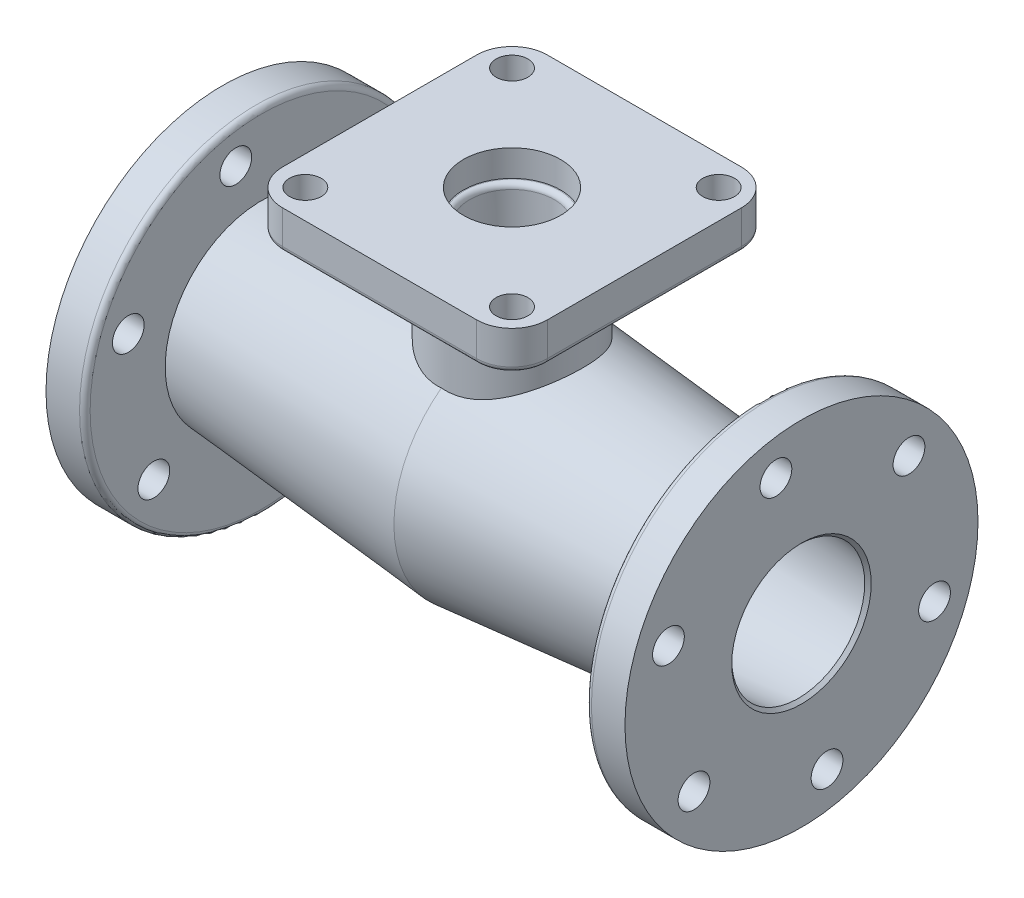
SolidWorks part; units mm, degrees
ref_plane "Front Plane" through (0, 0, 0) normal (0, 0, 1) x (1, 0, 0)
ref_plane "Top Plane" through (0, 0, 0) normal (0, 1, 0) x (1, 0, 0)
ref_plane "Right Plane" through (0, 0, 0) normal (1, 0, 0) x (0, 0, -1)
sketch "Sketch1" plane through (0, 0, 0) normal (0, 0, 1) x (1, 0, 0)
  line L0 (0, 0) -> (0, -50000) construction
  line L1 (0, 0) -> (-50000, 0) construction
  line L2 (0, -51.8481) -> (-164, -37.5)
  line L3 (-164, -37.5) -> (-164, -100)
  line L4 (-164, -100) -> (-142, -100)
  line L5 (-142, -100) -> (-142, -54.482)
  line L6 (-142, -54.482) -> (0, -66.9054)
  line L7 (142, -100) -> (142, -54.482)
  line L8 (164, -100) -> (142, -100)
  line L9 (164, -37.5) -> (164, -100)
  line L10 (0, -51.8481) -> (164, -37.5)
  line L11 (142, -54.482) -> (0, -66.9054)
  point P17 (-19.9552, -116.4925)
  point P18 (68.5947, -108.0282)
  dimension "D1" = 5
  dimension "D2" = 22
  dimension "D3" = 284
  dimension "D4" = 15
  dimension "D5" = 328
  dimension "D6" = 200
  dimension "D7" = 75
revolve "Revolve1" add sketch "Sketch1" angle 360 about L1
ref_plane "Plane1" through (0, 132, 0) normal (0, 1, 0) x (1, 0, 0)
sketch "Sketch3" plane through (0, 132, 0) normal (0, 1, 0) x (1, 0, 0)
  line L1 (-55, 75) -> (55, 75)
  line L2 (-75, 55) -> (-75, -55)
  line L3 (-55, -75) -> (55, -75)
  line L4 (75, 55) -> (75, -55)
  line L5 (-75, 75) -> (75, -75) construction
  line L6 (-75, -75) -> (75, 75) construction
  circle A0 centre (0, 0) radius 40
  circle A1 centre (-58.54, -58.54) radius 9
  circle A2 centre (58.54, -58.54) radius 9
  circle A3 centre (58.54, 58.54) radius 9
  circle A4 centre (-58.54, 58.54) radius 9
  arc A5 (-55, 75) -> (-75, 55) centre (-55, 55) ccw
  arc A6 (55, 75) -> (75, 55) centre (55, 55) cw
  arc A7 (55, -75) -> (75, -55) centre (55, -55) ccw
  arc A8 (-75, -55) -> (-55, -75) centre (-55, -55) ccw
  dimension "D1" = 80
  dimension "D4" = 18
  dimension "D5" = 20
  dimension "D2" = 150
  dimension "D3" = 150
extrude "Boss-Extrude1" add sketch "Sketch3" against normal blind 22 separate body
extrude "Boss-Extrude3" add sketch "Sketch3<3>" against normal up to next contours A0 region at (0, 132, 0)
sketch "Sketch3<3>" plane through (0, 132, 0) normal (0, 1, 0) x (1, 0, 0) same geometry as "Sketch3"
sketch "Sketch4" plane through (0, 0, 0) normal (0, 0, 1) x (1, 0, 0)
  line L0 (0, 0) -> (0, -50000) construction
  line L1 (0, 53.6315) -> (0, -66.9054) construction
  line L2 (0, 0) -> (21.9578, 0)
  line L3 (21.9578, 0) -> (24, 117)
  line L4 (24, 117) -> (27.5, 117)
  line L5 (27.5, 117) -> (27.5, 132)
  line L6 (27.5, 132) -> (0, 132)
  line L7 (0, 132) -> (0, 0)
  line L8 (-55, 132) -> (55, 132) construction
  point P5 (0, -6.637)
  dimension "D1" = 55
  dimension "D2" = 48
  dimension "D3" = 15
  dimension "D4" = 1
  dimension "D5" = 1
revolve "Cut-Revolve1" cut sketch "Sketch4" angle 360 about L0
fillet "Fillet1" radius 3 10 edges at (-69.1421, 110, 69.1421) (-75, 110, 0) (-69.1421, 110, -69.1421) (0, 110, -75) (69.1421, 110, -69.1421) (75, 110, 0) (69.1421, 110, 69.1421) (-142, 0, -100) (142, 0, -100) (0, 110, 75)
chamfer "Chamfer1" distance 2 angle 45 2 edges at (-164, 0, -37.5) (164, 0, -37.5) first distance on face at (-164, 0, -37.5) first distance on face at (164, 0, -37.5)
fillet "Fillet2" radius 3 1 edges at (-24, 117, 0)
hole_wizard "Ø5.0mm Dowel Hole1" positions "Sketch5" profile "Sketch6" hole size "Ø5.0" standard "AS" end condition up to next
sketch "Sketch5" plane through (164, 0, 0) normal (1, 0, 0) x (0, 0, -1)
  line L1 (0, 0) -> (-50000, 0) construction
  line L2 (0, 0) -> (-48296.2913, -12940.9523) construction
  circle A1 centre (0, 0) radius 80 construction
  point P0 (75.3761, -26.8039)
  dimension "D2" = 160
  dimension "D1" = 15
sketch "Sketch6" plane through (164, -26.8039, -75.3761) normal (0, 1, 0) x (0, 0, -1)
  line L0 (0, 0) -> (0, 22)
  line L1 (0, 22) -> (9, 22)
  line L2 (9, 22) -> (9, 0)
  line L5 (9, 0) -> (0, 0)
  line L11 (0, -6.35) -> (0, 107.95) construction
  dimension "Thru Hole Dia." = 18
  dimension "Thru Hole Depth" = 22
pattern_circular "CirPattern1" count 6 over 360 about axis through (0, 0, 0) along (-1, 0, 0) of "Ø5.0mm Dowel Hole1" reverse direction yes
mirror "Mirror1" about plane through (0, 0, 0) normal (1, 0, 0) of "CirPattern1"
